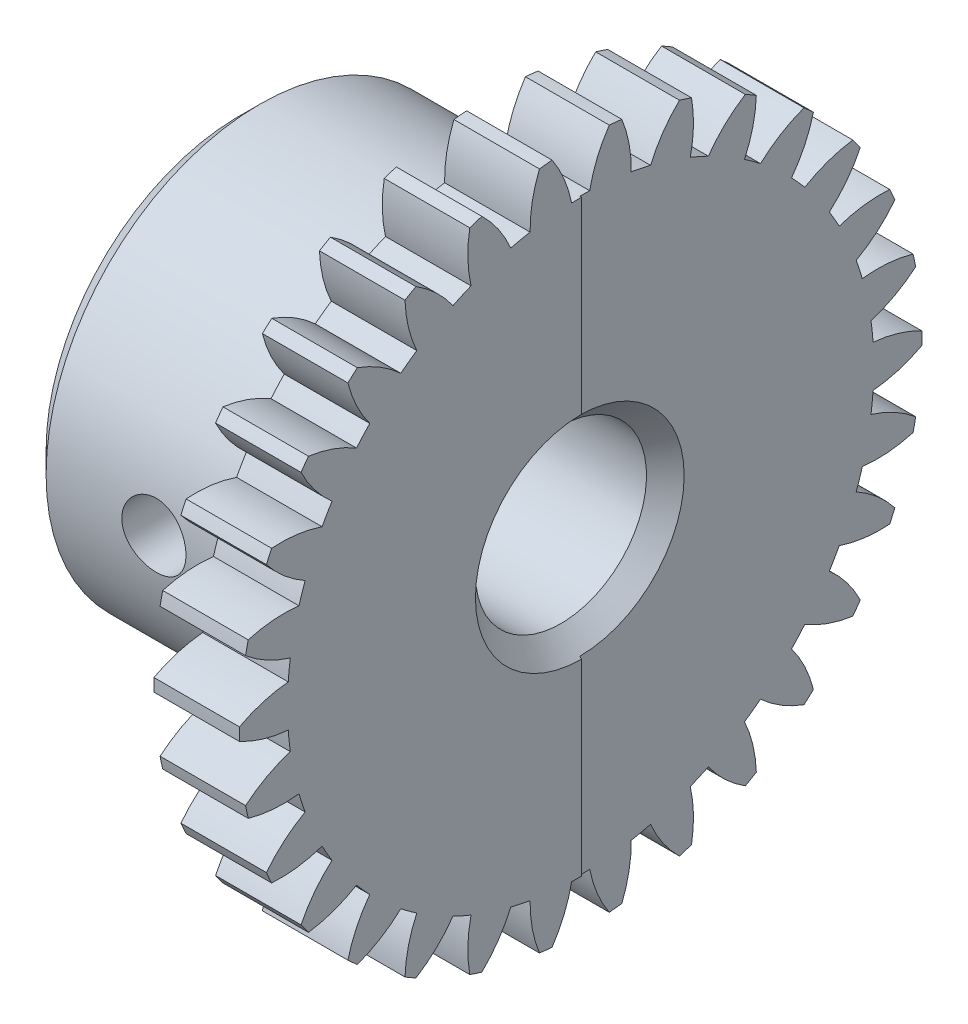
SolidWorks part; units mm, degrees
material "AISI 316 Stainless Steel Sheet (SS)"
ref_plane "Plane1" through (0, 0, 0) normal (0, 0, 1) x (1, 0, 0)
ref_plane "Plane2" through (0, 0, 0) normal (0, 1, 0) x (1, 0, 0)
ref_plane "Plane3" through (0, 0, 0) normal (1, 0, 0) x (0, 0, -1)
sketch "HoldingSke" plane through (0, 0, 0) normal (0, 1, 0) x (1, 0, 0)
  line L0 (0, 0) -> (351.9527, -203.2)
  line L1 (-15, 0) -> (100, 0) construction
  line L2 (0, 0) -> (-2.1039, 2.3779)
  line L3 (0, 0) -> (-11.863, 4.5341)
  line L4 (0, 0) -> (7.479, 4.318)
  line L5 (0, 0) -> (-23.7986, -8.8762)
  line L6 (0, 0) -> (-5.2639, -3.5516)
  line L7 (-2.1039, 2.3779) -> (3.3635, 27.1825)
  line L8 (-76.2, 54.61) -> (-61.976, 54.61)
  line L9 (-71.009, 38.7566) -> (-53.1078, 45.2721)
  line L10 (-76.2, 71.12) -> (104.1128, 71.12)
  line L11 (0, 0) -> (-6.35, 0)
  line L12 (-76.2, 101.6) -> (-76.1428, 101.6)
  line L13 (24.9733, 27.94) -> (52.9518, 28.4284)
  line L14 (24.9733, 27.94) -> (24.9746, 27.94)
  line L15 (24.9733, 27.94) -> (100.4006, 29.5858)
  circle A0 centre (0, 0) radius 6.35
  circle A1 centre (0, 0) radius 15.875
  circle A2 centre (0, 0) radius 15.875
  circle A3 centre (0, 0) radius 6.35
  dimension "MHD" = 31.75
  dimension "Hub_dia" = 31.75
  dimension "Bore" = 12.7
  dimension "MBD" = 12.7
  dimension "Num_teeth" = 30
  dimension "Pitch_radius" = 180.3128
  dimension "Pitch" = 406.4
  dimension "Width" = 6.35
  dimension "Overall_len" = 25.4
  dimension "Show_teeth" = 30
  dimension "Thickness" = 6.35
  dimension "OAL" = 25.4001
  dimension "T_dim" = 14.224
  dimension "Ap" = 20
  dimension "H" = 19.05
  dimension "Backlash" = 0.0571
  dimension "Addendum_fac" = 1
  dimension "Dedendum_fac" = 1.25
  dimension "Clearance_fac" = 0.25
  dimension "Dedendum_add" = 0.0013
sketch "BasProSke" plane through (0, 0, 0) normal (0, 1, 0) x (1, 0, 0)
  line L0 (-10, 0) -> (60, 0) construction
  line L1 (0, 0) -> (0, 25.4)
  line L2 (0, 0) -> (6.35, 0)
  line L3 (6.35, 0) -> (6.35, 25.4)
  line L4 (6.35, 25.4) -> (0, 25.4)
  dimension "Diameter" = 50.8
  dimension "Thickness" = 6.35
revolve "Base-Revolve" add sketch "BasProSke" angle 360 about L0
sketch "TooCutSke" plane through (0, 0, 0) normal (1, 0, 0) x (0, 0, -1)
  line L1 (0, 0) -> (0, 107) construction
  line L2 (0, 0) -> (-1.3462, 23.7744) construction
  line L3 (0, 0) -> (-4.9724, 47.3092) construction
  line L4 (-1.3462, 23.7744) -> (-2.4862, 23.6546) construction
  arc A0 (0.7354, 21.8145) -> (-0.7354, 21.8145) centre (0, 0) ccw
  arc A1 (2.2029, 25.3298) -> (-2.2029, 25.3298) centre (0, 0) ccw
  circle A2 centre (0, 0) radius 23.8125 construction
  circle A3 centre (0, 0) radius 22.3764 construction
  arc A4 (-0.7354, 21.8145) -> (-2.2029, 25.3298) centre (-10.0814, 19.9767) ccw
  arc A5 (2.2029, 25.3298) -> (0.7354, 21.8145) centre (10.0814, 19.9767) ccw
  dimension "Root_dia" = 43.6537
  dimension "Overcut_dia" = 50.8508
  dimension "Pitch_dia" = 47.625
  dimension "Base_dia" = 44.7529
  dimension "Flank_rad" = 9.525
  dimension "Half_ang" = 6
  dimension "Half_CT" = 1.1462
extrude "ToothCut" cut sketch "TooCutSke" along normal through all
fillet "Breaks" [suppressed] radius 0.0318 tangent propagation no
fillet "RootFillets" [suppressed] radius 0.3981
pattern_circular "TeethCuts" count 30 every 12 about axis through (-10, 0, 0) along (1, 0, 0) of "ToothCut", "RootFillets", "Breaks"
sketch "HubNeaOneSke" plane through (0, 0, 0) normal (-1, 0, 0) x (0, 0, 1)
  circle A0 centre (0, 0) radius 15.875
  dimension "Diameter" = 31.75
extrude "HubNearOne" add sketch "HubNeaOneSke" along normal blind 19.0501
sketch "HubNeaBotSke" plane through (0, 0, 0) normal (-1, 0, 0) x (0, 0, 1)
  circle A0 centre (0, 0) radius 15.875
  dimension "Diameter" = 31.75
extrude "HubNearBoth" [suppressed] add sketch "HubNeaBotSke" along normal blind 9.525
ref_plane "FarPln" through (6.35, 0, 0) normal (1, 0, 0) x (0, 0, -1)
sketch "HubFarSke" plane through (6.35, 0, 0) normal (1, 0, 0) x (0, 0, -1)
  circle A0 centre (0, 0) radius 15.875
  dimension "Diameter" = 31.75
extrude "HubFar" [suppressed] add sketch "HubFarSke" along normal blind 9.525
sketch "BorSke" plane through (0, 0, 0) normal (1, 0, 0) x (0, 0, -1)
  circle A0 centre (0, 0) radius 6.35
  dimension "Diameter" = 12.7
extrude "Bore" cut sketch "BorSke" along normal mid plane 50.8001
sketch "KeySke" plane through (0, 0, 0) normal (1, 0, 0) x (0, 0, -1)
  line L0 (-1.5875, 0) -> (-1.5875, 7.874)
  line L1 (-1.5875, 7.874) -> (1.5875, 7.874)
  line L2 (1.5875, 7.874) -> (1.5875, 0)
  line L3 (0, 0) -> (0, 34) construction
  line L4 (-1.5875, 0) -> (1.5875, 0)
  dimension "Offset" = 7.874
  dimension "Width" = 3.175
extrude "Keyway" [suppressed] cut sketch "KeySke" along normal mid plane 50.8001
pattern_circular "Keyway2" [suppressed] count 2 every 90 about axis through (-10, 0, 0) along (1, 0, 0)
chamfer "Chamfer1" distance 1.524 angle 45 2 edges at (0, 0, -15.875) (-19.0501, 0, 15.875)
chamfer "Chamfer2" distance 1.524 angle 45 2 edges at (6.35, 0, 6.35) (-19.0501, 0, 6.35)
sketch "Sketch1" plane through (0, 0, 0) normal (0, 0, 1) x (1, 0, 0)
  line L0 (-17.5261, 0) -> (-1.524, 0) construction
  line L1 (-17.5261, -15.875) -> (-17.5261, 15.875) construction
  line L2 (-1.524, -15.875) -> (-1.524, 15.875) construction
  circle A0 centre (-9.525, 0) radius 2.3813
  dimension "D1" = 4.7625
extrude "Cut-Extrude1" cut sketch "Sketch1" against normal through all and the other way through all
sketch "Sketch2" plane through (6.35, 0, 0) normal (1, 0, 0) x (0, 0, -1)
  line L0 (0, -28.9882) -> (0, 34.9728)
  line L1 (0, 34.9728) -> (32.2299, 34.9728)
  line L2 (32.2299, 34.9728) -> (32.2299, -28.9882)
  line L3 (32.2299, -28.9882) -> (0, -28.9882)
  dimension "D1" = 32.2299
  dimension "D2" = 63.961
  dimension "D3" = 34.9728
extrude "Cut-Extrude2" cut sketch "Sketch2" against normal blind 0.127
equation "' \"Pitch@HoldingSke\" = 4"
equation "' \"Num_teeth@HoldingSke\" = 12"
equation "' \"Ap@HoldingSke\" =  20"
equation "' \"Width@HoldingSke\" = 0.5"
equation "' \"Hub_dia@HoldingSke\"= 1"
equation "' \"Overall_len@HoldingSke\" = 1.0"
equation "' \"Bore@HoldingSke\" = 0.75"
equation "' \"T_dim@HoldingSke\" = 0.85"
equation "' \"Width@KeySke\" = 0.25"
equation "' \"Show_teeth@HoldingSke\" = 13"
equation "' \"Backlash@HoldingSke\" = 0.009"
equation "' \"Addendum_fac@HoldingSke\" = 1.0"
equation "' \"Dedendum_fac@HoldingSke\" = 1.25"
equation "' \"Dedendum_add@HoldingSke\" = 0.00005"
equation "' \"Clearance_fac@HoldingSke\" = 0.25"
equation "' \"Pitch@HoldingSke\" = 0.5"
equation "' \"Num_teeth@HoldingSke\" = 23"
equation "' \"Show_teeth@HoldingSke\" = 23"
equation "' \"Backlash@HoldingSke\" = 0.0375"
equation "\"Overcut_dia@TooCutSke\" = (\"Num_teeth@HoldingSke\" + 2 * \"Addendum_fac@HoldingSke\") / \"Pitch@HoldingSke\" + 0.002"
equation "\"Pitch_dia@TooCutSke\" = \"Num_teeth@HoldingSke\" / \"Pitch@HoldingSke\""
equation "\"Base_dia@TooCutSke\" = \"Num_teeth@HoldingSke\" / \"Pitch@HoldingSke\" * cos((\"Ap@HoldingSke\"  * 3.14159265 / 180))"
equation "\"Root_dia@TooCutSke\" = (\"Num_teeth@HoldingSke\" + 2) / \"Pitch@HoldingSke\" - 2 * (\"Addendum_fac@HoldingSke\" + \"Dedendum_fac@HoldingSke\") / \"Pitch@HoldingSke\" - \"Dedendum_add@HoldingSke\" * 2"
equation "\"Half_ang@TooCutSke\" = 180 / \"Num_teeth@HoldingSke\""
equation "\"Half_CT@TooCutSke\" = \"Num_teeth@HoldingSke\" / \"Pitch@HoldingSke\" * sin((3.14159265 / 2 / \"Num_teeth@HoldingSke\")) / 2 - 7 * \"Backlash@HoldingSke\" / 4"
equation "\"Flank_rad@TooCutSke\" = \"Num_teeth@HoldingSke\" / \"Pitch@HoldingSke\" / 5"
equation "\"Radius@RootFillets\" = \"Clearance_fac@HoldingSke\" / \"Pitch@HoldingSke\" + \"Dedendum_add@HoldingSke\""
equation "\"Break_rad@Breaks\" = 0.02 / \"Pitch@HoldingSke\""
equation "\"Thickness@HoldingSke\" = \"Width@HoldingSke\""
equation "\"OAL@HoldingSke\" = \"Thickness@HoldingSke\""
equation "\"MHD@HoldingSke\" = (\"Num_teeth@HoldingSke\" + 2) / \"Pitch@HoldingSke\" - 2 * (\"Addendum_fac@HoldingSke\" + \"Dedendum_fac@HoldingSke\")  / \"Pitch@HoldingSke\" - \"Dedendum_add@HoldingSke\" * 2"
equation "\"MBD@HoldingSke\" = (\"Num_teeth@HoldingSke\" + 2) / \"Pitch@HoldingSke\" - 2 * (\"Addendum_fac@HoldingSke\" + \"Dedendum_fac@HoldingSke\")  / \"Pitch@HoldingSke\" - \"Dedendum_add@HoldingSke\" * 2 - 0.002"
equation "\"MHD@HoldingSke\" = ((sgn( \"MHD@HoldingSke\" - \"Hub_dia@HoldingSke\" )-1)*( \"MHD@HoldingSke\" - \"Hub_dia@HoldingSke\" ))/-2+ \"Hub_dia@HoldingSke\""
equation "\"MBD@HoldingSke\" = ((sgn( \"MBD@HoldingSke\" - \"Bore@HoldingSke\" )-1)*( \"MBD@HoldingSke\" - \"Bore@HoldingSke\" ))/-2+ \"Bore@HoldingSke\""
equation "\"OAL@HoldingSke\" = ((sgn( \"OAL@HoldingSke\" - \"Overall_len@HoldingSke\" )+1)*( \"OAL@HoldingSke\" - \"Overall_len@HoldingSke\" ))/2 + \"Overall_len@HoldingSke\" + 0.000002"
equation "\"Num_teeth@TeethCuts\" = int( \"Show_teeth@HoldingSke\" ) + 1"
equation "\"Num_teeth@TeethCuts\" = ((sgn( \"Num_teeth@TeethCuts\" - \"Num_teeth@HoldingSke\" )-1)*( \"Num_teeth@TeethCuts\" - \"Num_teeth@HoldingSke\" ))/-2+ \"Num_teeth@HoldingSke\""
equation "\"Num_teeth@TeethCuts\" = ((sgn( \"Num_teeth@TeethCuts\" - 2.0)+1)*( \"Num_teeth@TeethCuts\" - 2.0))/2 +2.0"
equation "\"Angle@TeethCuts\" = 360.0 / \"Num_teeth@HoldingSke\""
equation "\"Diameter@BasProSke\" = (\"Num_teeth@HoldingSke\" + 2 * \"Addendum_fac@HoldingSke\") / \"Pitch@HoldingSke\""
equation "\"Thickness@BasProSke\"  = \"Thickness@HoldingSke\""
equation "' \"Fillet_rad@BasProSke\" =  \"Thickness@HoldingSke\" * 0.05"
equation "\"MHD@HoldingSke\" = ((sgn( \"MHD@HoldingSke\" - \"Root_dia@TooCutSke\" )-1)*( \"MHD@HoldingSke\" - \"Root_dia@TooCutSke\" ))/-2+ \"Root_dia@TooCutSke\""
equation "\"Diameter@HubNeaOneSke\" = \"MHD@HoldingSke\""
equation "\"Length@HubNearOne\" = \"OAL@HoldingSke\" - \"Thickness@BasProSke\""
equation "\"Diameter@HubNeaBotSke\" = \"MHD@HoldingSke\""
equation "\"Length@HubNearBoth\" = ( \"OAL@HoldingSke\" - \"Thickness@BasProSke\" ) / 2.0"
equation "\"Thickness@FarPln\" = \"Thickness@BasProSke\""
equation "\"Diameter@HubFarSke\" = \"MHD@HoldingSke\""
equation "\"Length@HubFar\" = ( \"OAL@HoldingSke\" - \"Thickness@BasProSke\" ) / 2.0"
equation "\"Diameter@BorSke\" = \"MBD@HoldingSke\""
equation "\"D1@Bore\" = \"OAL@HoldingSke\" * 2.0"
equation "\"D1@Keyway\" = \"OAL@HoldingSke\" * 2.0"
equation "\"Offset@KeySke\" = \"T_dim@HoldingSke\" - \"MBD@HoldingSke\" / 2.0"
